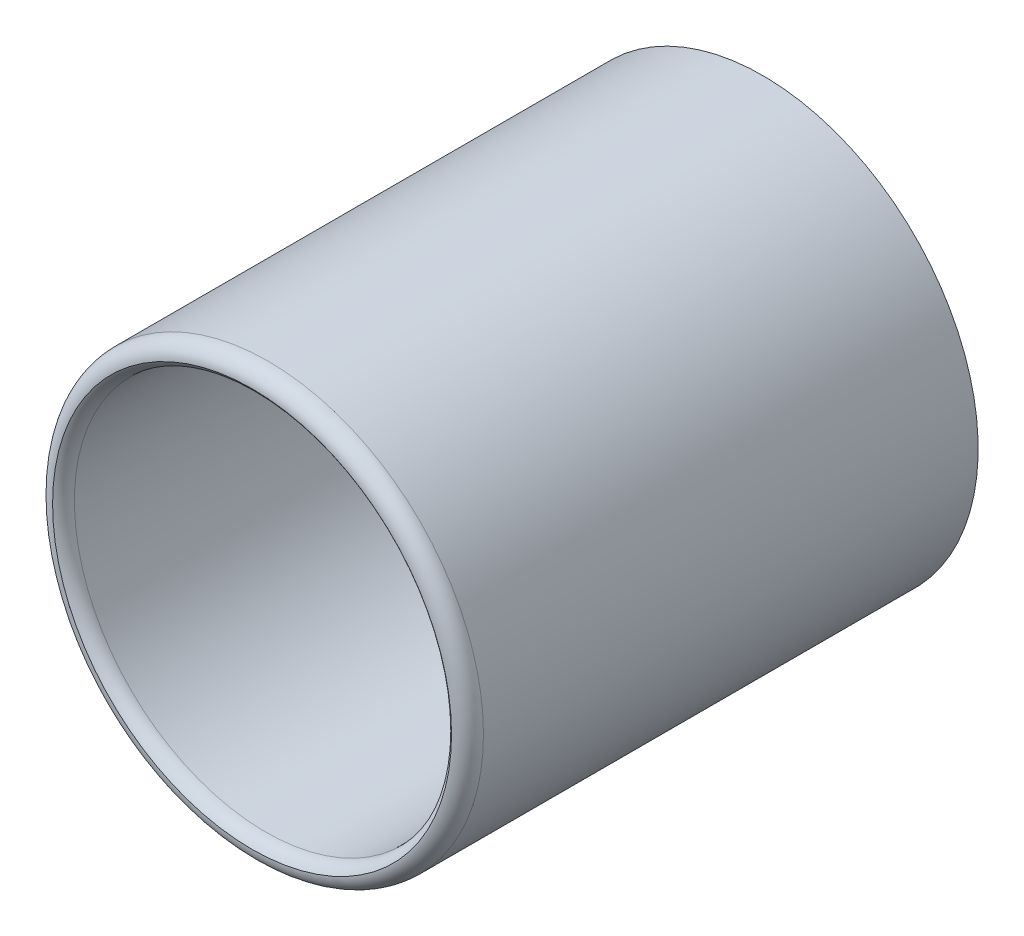
SolidWorks part; units mm, degrees
ref_plane "Ön Düzlem" through (0, 0, 0) normal (0, 0, 1) x (1, 0, 0)
ref_plane "Üst Düzlem" through (0, 0, 0) normal (0, 1, 0) x (1, 0, 0)
ref_plane "Sağ Düzlem" through (0, 0, 0) normal (1, 0, 0) x (0, 0, -1)
sketch "Çizim1" plane through (0, 0, 0) normal (0, 0, 1) x (1, 0, 0)
  circle A0 centre (0, 0) radius 67.5
  circle A1 centre (0, 0) radius 60
  dimension "D1" = 120
  dimension "D2" = 135
extrude "Yükseklik-Ekstrüzyon1" add sketch "Çizim1" along normal blind 150
sketch "Çizim2" plane through (0, 0, 0) normal (0, 0, -1) x (-1, 0, 0)
  circle A0 centre (0, 0) radius 67.5
extrude "Yükseklik-Ekstrüzyon2" add sketch "Çizim2" along normal blind 10
fillet "Radyus1" radius 5 1 edges at (67.5, 0, 150)
fillet "Radyus2" radius 5 1 edges at (60, 0, 150)
